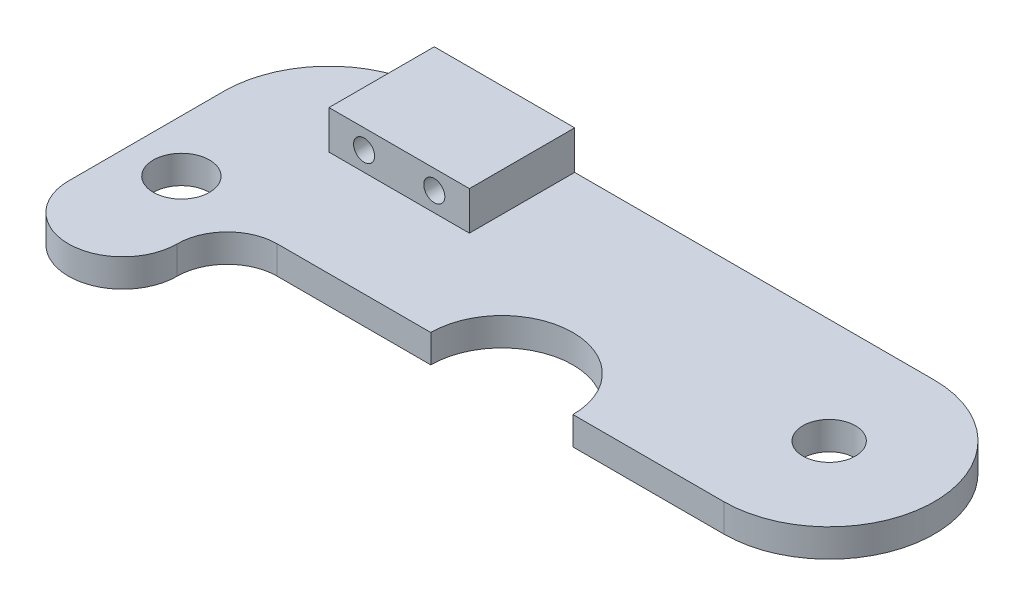
SolidWorks part; units mm, degrees
ref_plane "Front Plane" through (0, 0, 0) normal (0, 0, 1) x (1, 0, 0)
ref_plane "Top Plane" through (0, 0, 0) normal (0, 1, 0) x (1, 0, 0)
ref_plane "Right Plane" through (0, 0, 0) normal (1, 0, 0) x (0, 0, -1)
sketch "Sketch1" plane through (0, 0, 0) normal (0, 1, 0) x (1, 0, 0)
  line L15 (39.0719, -176.8025) -> (67.5719, -176.8025)
  line L17 (42.1221, -188.8025) -> (50.8721, -188.8025)
  line L21 (33.0721, -182.7525) -> (33.0721, -191.6525)
  line L22 (33.0721, -191.6525) -> (39.2721, -191.6525) construction
  line L24 (42.1221, -191.6525) -> (42.1221, -188.8025) construction
  line L25 (58.9721, -188.8025) -> (67.5719, -188.8025)
  line L26 (50.8721, -188.8025) -> (58.9721, -188.8025)
  arc A10 (67.5719, -188.8025) -> (67.5719, -176.8025) centre (67.5719, -182.8025) ccw
  arc A12 (39.0719, -176.8025) -> (33.0721, -182.7525) centre (39.0719, -182.8025) ccw
  arc A14 (42.1221, -188.8025) -> (39.2721, -191.6525) centre (42.1221, -191.6525) ccw
  arc A15 (58.9721, -188.8025) -> (50.8721, -188.8025) centre (54.9221, -188.8025) ccw
  arc A16 (33.0721, -191.6525) -> (39.2721, -191.6525) centre (36.1721, -191.6525) ccw
  circle A17 centre (36.0529, -188.1938) radius 1.6
  circle A18 centre (67.5719, -182.8025) radius 1.5
  circle A19 centre (36.0529, -188.1938) radius 1.6 construction
  dimension "D1" = 3.1
  dimension "D2" = 4.05
  dimension "D3" = 8.75
  dimension "D4" = 2.85
  dimension "D5" = 6
  dimension "D6" = 6
  dimension "D7" = 8.9
  dimension "D9" = 3
  dimension "D12" = 90
  dimension "D10" = 3.2
  dimension "D13" = 0
  dimension "D8" = 28.5
  dimension "D11" = 0
extrude "Boss-Extrude1" add sketch "Sketch1" along normal blind 1.6 contours L21 A16 A14 L17 A15 L25 A10 L15 A12 A18 A17 region at (51.7129, 0, 183.1937)
sketch "Sketch2" plane through (0, 1.6, 0) normal (0, 1, 0) x (1, 0, 0)
  line L1 (39.0719, -176.8025) -> (47.0719, -176.8025)
  line L2 (39.0719, -176.8025) -> (39.0719, -182.8025)
  line L3 (39.0719, -182.8025) -> (47.0719, -182.8025)
  line L4 (47.0719, -176.8025) -> (47.0719, -182.8025)
  dimension "D1" = 6
  dimension "D2" = 8
extrude "Boss-Extrude2" add sketch "Sketch2" along normal blind 2.2
sketch "Sketch3" plane through (0, 0, 176.8025) normal (0, 0, -1) x (-1, 0, 0)
  line L0 (-47.0719, 3.8) -> (-39.0719, 3.8) construction
  line L1 (-39.0719, 3.8) -> (-39.0719, 1.6) construction
  line L2 (-47.0719, 3.8) -> (-47.0719, 1.6) construction
  circle A0 centre (-45.0719, 2.7) radius 0.6
  circle A1 centre (-41.0719, 2.7) radius 0.6
  dimension "D5" = 1.2
  dimension "D6" = 1.2
  dimension "D1" = 1.1
  dimension "D2" = 1.1
  dimension "D3" = 2
  dimension "D4" = 2
extrude "Cut-Extrude1" cut sketch "Sketch3" against normal up to next
